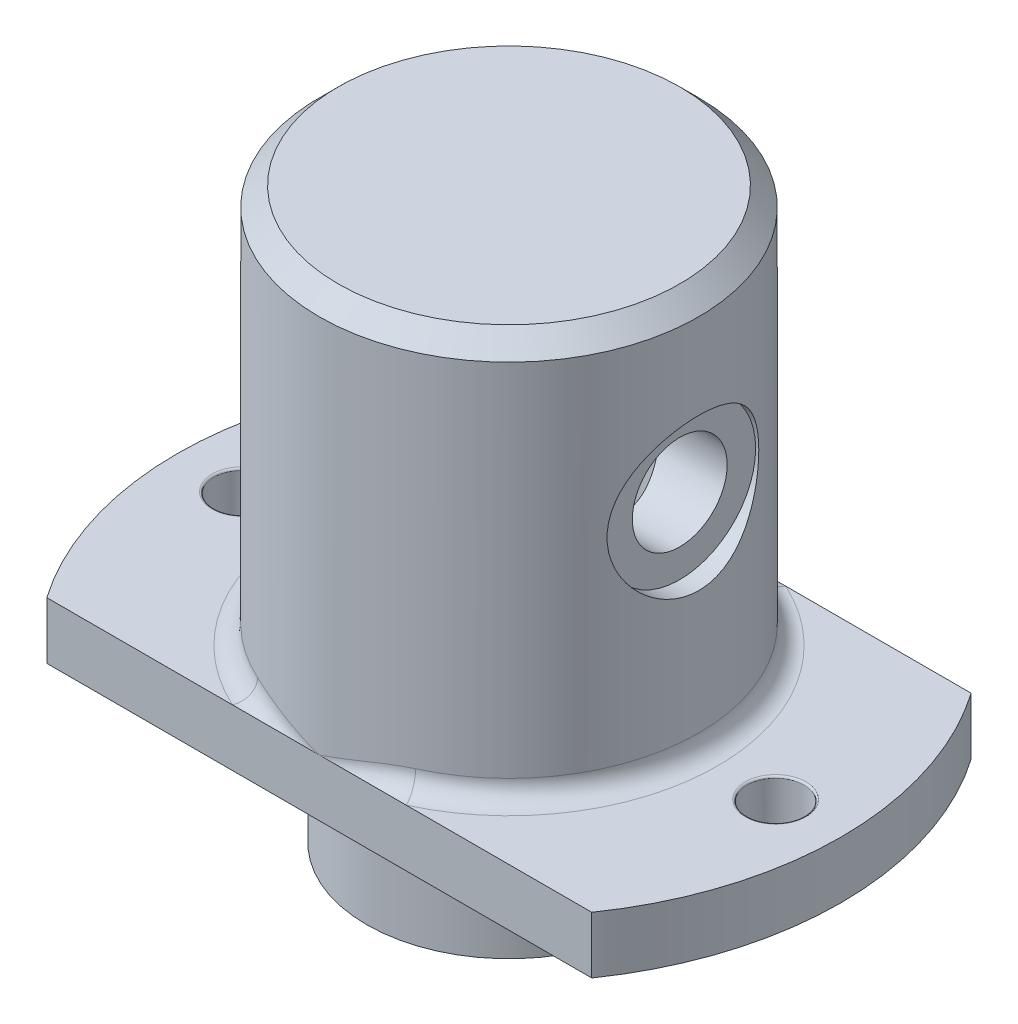
SolidWorks part; units mm, degrees
material "Brass"
ref_plane "Front Plane" through (0, 0, 0) normal (0, 0, 1) x (1, 0, 0)
ref_plane "Top Plane" through (0, 0, 0) normal (0, 1, 0) x (1, 0, 0)
ref_plane "Right Plane" through (0, 0, 0) normal (1, 0, 0) x (0, 0, -1)
sketch "Sketch1" plane through (0, 0, 0) normal (0, 0, 1) x (1, 0, 0)
  line L0 (0, 20.2279) -> (0, -9.7721)
  line L1 (0, -9.7721) -> (7.5, -9.7721)
  line L2 (7.5, -9.7721) -> (7.5, -3.7721)
  line L3 (7.5, -3.7721) -> (17.5, -3.7721)
  line L4 (17.5, -3.7721) -> (17.5, -0.7721)
  line L5 (17.5, -0.7721) -> (10, -0.7721)
  line L6 (10, -0.7721) -> (10, 20.2279)
  line L7 (10, 20.2279) -> (0, 20.2279)
  dimension "D1" = 30
  dimension "D2" = 7.5
  dimension "D3" = 10
  dimension "D4" = 3
  dimension "D5" = 6
  dimension "D6" = 17.5
revolve "Revolve1" add sketch "Sketch1" angle 360 about L0
sketch "Sketch2" plane through (0, -0.7721, 0) normal (0, 1, 0) x (1, 0, 0)
  line L1 (-14.3614, 10) -> (14.3614, 10)
  line L3 (-14.3614, -10) -> (14.3614, -10)
  line L5 (-21.6746, 10) -> (21.6746, -10) construction
  line L6 (-21.6746, -10) -> (21.6746, 10) construction
  circle A0 centre (0, 0) radius 17.5 construction
  circle A1 centre (0, 0) radius 17.5
  point P0 (0, 0)
  circle M3 centre (0, 0) radius 17.5
  dimension "D1" = 20
extrude "Cut-Extrude1" cut sketch "Sketch2" against normal mid plane 10 contours L3 M3 | L1 M3
fillet "Fillet1" radius 1 2 edges at (10, -0.7721, 0) (-10, -0.7721, 0)
chamfer "Chamfer1" distance 1 angle 45 1 edges at (0, 20.2279, 10)
ref_plane "Plane1" through (10, 0, 0) normal (1, 0, 0) x (0, 0, -1)
sketch "Sketch5" plane through (10, 0, 0) normal (1, 0, 0) x (0, 0, -1)
  line L0 (-7.5, -9.7721) -> (7.5, -9.7721) construction
  circle A0 centre (0, 10.7279) radius 4
  dimension "D1" = 8
  dimension "D2" = 20.5
extrude "Cut-Extrude2" cut sketch "Sketch5" against normal blind 1
sketch "Sketch6" plane through (9, 0, 0) normal (1, 0, 0) x (0, 0, -1)
  circle A0 centre (0, 10.7279) radius 2.5
  dimension "D1" = 5
sketch "Sketch7" plane through (0, -0.7721, 0) normal (0, 1, 0) x (1, 0, 0)
  circle A0 centre (14.05, 0) radius 1.5
  dimension "D1" = 3
  dimension "D2" = 14.05
extrude "Cut-Extrude4" cut sketch "Sketch7" against normal blind 3
mirror "Mirror1" about plane through (0, 0, 0) normal (1, 0, 0) of "Cut-Extrude4"
fillet "Fillet2" radius 0.1 4 edges at (-14.05, -0.7721, 1.5) (-14.05, -3.7721, 1.5) (14.05, -0.7721, 1.5) (14.05, -3.7721, 1.5)
sketch "Sketch8" plane through (0, -9.7721, 0) normal (0, -1, 0) x (1, 0, 0)
  circle A0 centre (0, 0) radius 6
  dimension "D1" = 12
extrude "Cut-Extrude7" cut sketch "Sketch8" against normal blind 25
extrude "Cut-Extrude8" cut sketch "Sketch6" against normal up to next
